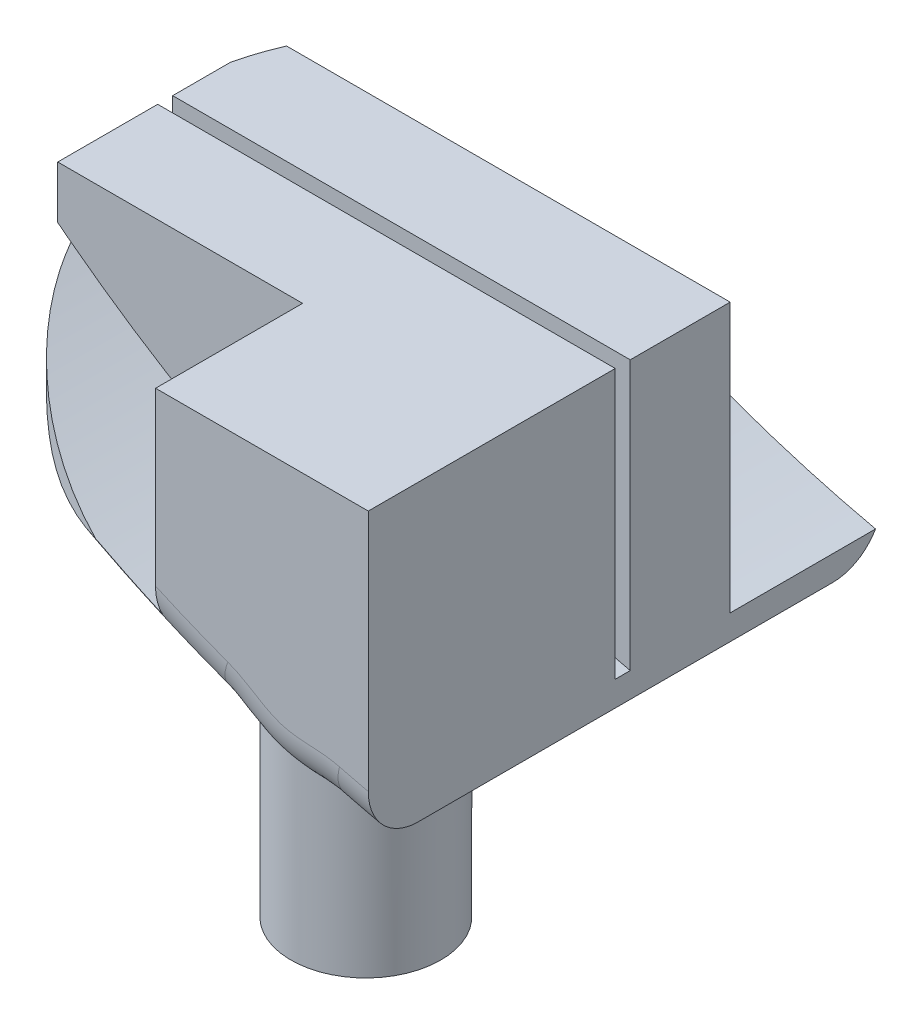
SolidWorks part; units mm, degrees
ref_plane "Front Plane" through (0, 0, 0) normal (0, 0, 1) x (1, 0, 0)
ref_plane "Top Plane" through (0, 0, 0) normal (0, 1, 0) x (1, 0, 0)
ref_plane "Right Plane" through (0, 0, 0) normal (1, 0, 0) x (0, 0, -1)
sketch "Sketch1" plane through (0, 0, 0) normal (0, 1, 0) x (1, 0, 0)
  line L1 (-101.7931, 82.9144) -> (50.6503, 82.9144)
  line L2 (-101.7931, 82.9144) -> (-101.7931, -53.7229)
  line L3 (-101.7931, -53.7229) -> (50.6503, -53.7229)
  line L4 (50.6503, 82.9144) -> (50.6503, -53.7229)
  line L5 (-101.7931, 82.9144) -> (50.6503, -53.7229) construction
  line L6 (-101.7931, -53.7229) -> (50.6503, 82.9144) construction
  point P0 (-25.5714, 14.5958)
extrude "Boss-Extrude1" add sketch "Sketch1" along normal blind 200
sketch "Sketch2" plane through (0, 0, 0) normal (0, 0, 1) x (1, 0, 0)
  line L2 (-83, 153) -> (-80, 153)
  line L4 (-155, -69.5) -> (-155, -64.5)
  line L9 (-155, -64.5) -> (-152, -64.5)
  line L12 (-152, -64.5) -> (-152, -59.5)
  line L13 (-152, -59.5) -> (-155, -59.5)
  line L14 (-155, -59.5) -> (-155, -54.0482)
  line L15 (-288.0952, 47) -> (-296.5952, 47)
  line L17 (-296.5952, 47) -> (-296.5952, 44)
  line L19 (-296.5952, 44) -> (-287.9228, 44)
  line L21 (-83, 160.5) -> (-80, 160.5)
  line L22 (-80, 160.5) -> (-80, 153)
  line L23 (-83, 153) -> (-83, 145.5)
  parabola Q1 (-155, -69.5) -> (-306.0893, 45.5) focus (-179.0197, 57.3821) apex (-244.7409, -27.552)
  spline S1 degree 3 poles (-83, 160.5) (-186.6749, 160.5) (-259.8996, 132.37) (-306.0893, 45.5) knots 0 0 0 0 1 1 1 1
  spline S2 degree 1 poles (-151.4967, -54.9148) (-288.8909, 45.6217) knots 0 0 1 1 construction
  spline S3 degree 1 poles (-83, 145.5) (-288.8909, 45.6217) knots 0 0 1 1 construction
  spline S4 degree 3 poles (-151.4967, -54.9148) (-153.3988, -54.458) (-157.2086, -53.4983) (-164.6601, -51.4419) (-173.7484, -48.594) (-184.2693, -44.7413) (-197.7998, -39.024) (-213.7896, -30.7928) (-231.5494, -19.1756) (-247.9291, -5.7971) (-260.462, 6.8492) (-269.8307, 17.8876) (-276.5289, 26.6314) (-281.8406, 34.3147) (-285.9211, 40.691) (-287.9161, 43.9748) (-288.8909, 45.6217) knots 0.497669 0.497669 0.497669 0.497669 0.497806 0.497943 0.498217 0.498491 0.498765 0.499314 0.499862 0.500411 0.500959 0.501233 0.501508 0.501782 0.501919 0.502056 0.502056 0.502056 0.502056 only from (-155, -54.0482) to (-287.9228, 44)
  spline S5 degree 3 poles (-288.8909, 45.6217) (-288.2118, 46.8068) (-286.8274, 49.1771) (-284.0331, 53.7809) (-280.4563, 59.3452) (-276.0412, 65.7051) (-269.9863, 73.7792) (-262.1032, 83.1283) (-252.1296, 93.2247) (-241.6235, 102.2655) (-226.87, 112.9967) (-206.9505, 124.0773) (-184.8372, 132.3478) (-165.7316, 137.4023) (-150.6813, 140.4388) (-134.8993, 142.7481) (-121.1337, 144.0897) (-109.751, 144.8283) (-101.0301, 145.2187) (-93.6051, 145.4111) (-87.5802, 145.4874) (-84.523, 145.5) (-83, 145.5) knots 0 0 0 0 0.015161 0.030323 0.060645 0.090968 0.12129 0.181936 0.242581 0.303226 0.363871 0.485162 0.606452 0.667098 0.727743 0.788388 0.849033 0.879356 0.909679 0.940001 0.955163 0.970324 0.970324 0.970324 0.970324 only from (-288.0952, 47) to (-83, 145.5)
  dimension "D2" = 7.5
  dimension "D3" = 5
  dimension "D4" = 5
  dimension "D5" = 8.5
  dimension "D1" = 15
sketch "Sketch3" plane through (-101.7931, 0, 0) normal (-1, 0, 0) x (0, 0, 1)
  line L1 (53.7229, 0) -> (-82.9144, 0)
  line L2 (53.7229, 0) -> (53.7229, 200)
  line L3 (53.7229, 200) -> (-82.9144, 200)
  line L4 (-82.9144, 0) -> (-82.9144, 200)
extrude "Boss-Extrude2" add sketch "Sketch3" along normal blind 220
sketch "Sketch4" plane through (0, 0, 0) normal (0, -1, 0) x (-1, 0, 0)
  line L1 (321.7931, 82.9144) -> (-50.6503, 82.9144)
  line L2 (321.7931, 82.9144) -> (321.7931, -53.7229)
  line L3 (321.7931, -53.7229) -> (-50.6503, -53.7229)
  line L4 (-50.6503, 82.9144) -> (-50.6503, -53.7229)
extrude "Boss-Extrude3" add sketch "Sketch4" along normal blind 80
sketch "Sketch5" plane through (0, 0, 0) normal (0, 0, 1) x (1, 0, 0)
  line L0 (-155, -69.5) -> (-155, -80)
  line L1 (50.6503, -80) -> (-321.7931, -80) construction
  line L2 (-155, -69.5) -> (-155, -54.0482)
  line L3 (-244.7409, -27.552) -> (-247.8008, -31.5064)
  line L5 (-155, -69.5) -> (-155, -74.5)
  arc A0 (-155, -69.5) -> (-244.7409, -27.552) centre (-105.1343, 154.1469) cw
  arc A1 (-155, -74.5) -> (-247.8008, -31.5064) centre (-104.6153, 155.9057) cw
extrude "Boss-Extrude4" add sketch "Sketch5" along normal blind 180 contours L5 A1 L3 A0
sketch "Sketch6" plane through (0, 0, 53.7229) normal (0, 0, 1) x (1, 0, 0)
  line L0 (50.6503, -80) -> (-321.7931, -80) construction
  line L1 (-260.7437, -80) -> (-154.9156, -80)
  line L2 (-260.7437, -80) -> (-260.7437, 10.4738)
  line L3 (-260.7437, 10.4738) -> (-154.9156, 10.4738)
  line L4 (-154.9156, -80) -> (-154.9156, 10.4738)
  line L6 (-260.7437, 10.4738) -> (-302.077, 10.4738)
  line L7 (-260.7437, 10.4738) -> (-260.7437, -1.896)
  line L8 (-260.7437, -1.896) -> (-302.077, -1.896)
  line L9 (-302.077, 10.4738) -> (-302.077, -1.896)
  line L10 (-154.9156, 10.4738) -> (-246.5701, 10.4738)
  line L11 (-154.9156, 10.4738) -> (-154.9156, -15.638)
  line L12 (-154.9156, -15.638) -> (-246.5701, -15.638)
  line L13 (-246.5701, 10.4738) -> (-246.5701, -15.638)
extrude "Boss-Extrude6" add sketch "Sketch6" along normal blind 160 contours L3 L13 L12 L4 region at (-200.7429, -2.5821, 53.7229)
sketch "Sketch8" plane through (0, -15.638, 0) normal (0, -1, 0) x (-1, 0, 0)
  line L0 (246.5701, -213.7229) -> (246.5701, -53.7229) construction
  line L1 (246.5701, -82.8166) -> (154.9156, -82.8166)
  line L2 (246.5701, -82.8166) -> (246.5701, -102.8166)
  line L3 (246.5701, -102.8166) -> (154.9156, -102.8166)
  line L4 (154.9156, -82.8166) -> (154.9156, -102.8166)
  line L5 (154.9156, -213.7229) -> (154.9156, -53.7229) construction
  line L6 (154.9156, -102.8166) -> (154.9156, -105.8166)
  line L8 (154.9156, -105.8166) -> (246.5701, -105.8166)
  line L9 (154.9156, -105.8166) -> (154.9156, -125.8166)
  line L10 (154.9156, -125.8166) -> (246.5701, -125.8166)
  line L11 (246.5701, -105.8166) -> (246.5701, -125.8166)
  line M8 (154.9156, -53.7229) -> (154.9156, -213.7229)
  line M10 (246.5701, -213.7229) -> (246.5701, -53.7229)
  dimension "D1" = 20
  dimension "D2" = 20
  dimension "D3" = 3
extrude "Boss-Extrude7" add sketch "Sketch8" along normal up to surface (53.8808 mm away) contours L10 L8 M8 M10 | L3 L1 M10 M8 region at (-200.7429, -15.638, 92.8166) region at (-200.7429, -15.638, 115.8166) up to face at (-201.0175, -50.9798, 116.8614)
sketch "Sketch9" plane through (0, -15.638, 0) normal (0, -1, 0) x (-1, 0, 0)
  line L0 (154.9156, -125.8166) -> (154.9156, -135.8166) construction
  line L1 (154.9156, -213.7229) -> (154.9156, -125.8166) construction
  line L2 (154.9156, -135.8166) -> (174.9156, -135.8166) construction
  circle A0 centre (174.9156, -135.8166) radius 15
extrude "Boss-Extrude8" add sketch "Sketch9" along normal blind 90
sketch "Sketch10" plane through (0, -15.638, 0) normal (0, -1, 0) x (-1, 0, 0)
  line L0 (154.9156, -213.7229) -> (154.9156, -125.8166) construction
  line L1 (246.5701, -125.8166) -> (154.9156, -125.8166)
  line L2 (246.5701, -125.8166) -> (246.5701, -155.2396)
  line L3 (246.5701, -155.2396) -> (154.9156, -155.2396)
  line L4 (154.9156, -125.8166) -> (154.9156, -155.2396)
  line L6 (154.9156, -125.8166) -> (197.5697, -125.8166)
  line L7 (154.9156, -125.8166) -> (154.9156, -155.2396)
  line L8 (154.9156, -155.2396) -> (197.5697, -155.2396)
  line L9 (197.5697, -125.8166) -> (197.5697, -155.2396)
  arc M2 (186.0959, -125.8166) -> (163.7353, -125.8166) centre (174.9156, -135.8166) cw
  line M3 (163.7353, -125.8166) -> (154.9156, -125.8166)
  line M4 (154.9156, -125.8166) -> (154.9156, -213.7229)
extrude "Boss-Extrude9" add sketch "Sketch10" along normal up to surface (39.882 mm away) contours L9 L1 L3 M2 M3 M4 region at (-197.0516, -15.638, 140.5281) up to face at (-191.8541, -54.9413, 143.0605)
sketch "Sketch11" plane through (0, -105.638, 0) normal (0, -1, 0) x (-1, 0, 0)
  line L0 (189.9156, -135.8166) -> (159.9156, -135.8166) construction
  circle A0 centre (174.9156, -135.8166) radius 15 construction
  circle A1 centre (174.9156, -135.8166) radius 15 construction
  circle A2 centre (174.9156, -135.8166) radius 5
extrude "Cut-Extrude1" cut sketch "Sketch11" against normal blind 30 contours A2
sketch "Sketch12" plane through (0, -80, 0) normal (0, -1, 0) x (-1, 0, 0)
  line L1 (-50.6503, 82.9144) -> (321.7931, 82.9144)
  line L2 (-50.6503, 82.9144) -> (-50.6503, -53.7229)
  line L3 (-50.6503, -53.7229) -> (321.7931, -53.7229)
  line L4 (321.7931, 82.9144) -> (321.7931, -53.7229)
extrude "Cut-Extrude2" cut sketch "Sketch12" against normal blind 310
sketch "Sketch13" plane through (-154.9156, 0, 0) normal (1, 0, 0) x (0, 0, -1)
  line L1 (-53.7229, 10.4738) -> (-213.7229, 10.4738)
  line L2 (-53.7229, 10.4738) -> (-53.7229, -15.638)
  line L3 (-53.7229, -15.638) -> (-213.7229, -15.638)
  line L4 (-213.7229, 10.4738) -> (-213.7229, -15.638)
extrude "Cut-Extrude3" cut sketch "Sketch13" against normal blind 310
sketch "Sketch14" plane through (0, 0, 155.2396) normal (0, 0, 1) x (1, 0, 0)
  line L0 (-155, -69.5) -> (-155, -74.5) construction
  line L1 (-155, -69.5992) -> (-154.7887, -69.5992)
  line L2 (-155, -69.5992) -> (-155, -8.2779)
  line L3 (-155, -8.2779) -> (-154.7887, -8.2779)
  line L4 (-154.7887, -69.5992) -> (-154.7887, -8.2779)
  dimension "D1" = 61.3214
extrude "Cut-Extrude4" cut sketch "Sketch14" against normal blind 310 contours L2 L1 L4 L3
sketch "Sketch15" plane through (0, -15.638, 0) normal (0, 1, 0) x (1, 0, 0)
  line L0 (-200.7851, -102.8166) -> (-200.7851, -104.3166)
  line L1 (-155, -53.7229) -> (-247.8008, -53.7229)
  line L2 (-155, -53.7229) -> (-155, -180)
  line L3 (-155, -180) -> (-247.8008, -180)
  line L4 (-247.8008, -53.7229) -> (-247.8008, -180)
  line L5 (-246.5701, -102.8166) -> (-155, -102.8166) construction
  line L6 (-200.7851, -104.3166) -> (-155, -104.3166)
  line L7 (-200.7851, -104.3166) -> (-247.8008, -104.3166)
  line L8 (-247.8008, -104.3166) -> (-247.8008, -53.7229)
  line L9 (-231.1669, -104.3166) -> (-231.1669, -53.7229)
  line L10 (-231.1669, -104.3166) -> (-231.1669, -154.9166)
  line L11 (-231.1669, -154.9166) -> (-155, -155.2396)
  line L12 (-231.1669, -154.9166) -> (-247.8008, -154.9166)
  line L14 (-247.8008, -180) -> (-155, -180)
  line L15 (-247.8008, -180) -> (-247.8008, -155.2396)
  line L16 (-247.8008, -155.2396) -> (-155, -155.2396)
  line L17 (-155, -180) -> (-155, -155.2396)
extrude "Cut-Extrude5" cut sketch "Sketch15" against normal blind 310 contours L16 L4 L3 L2 region at (-201.4004, -15.638, 167.6198)
sketch "Sketch16" plane through (0, -15.638, 0) normal (0, 1, 0) x (1, 0, 0)
  line L0 (-247.8008, -104.4812) -> (-247.8008, -53.7229)
  line L1 (-247.8008, -155.2396) -> (-155, -155.2396)
  line L2 (-247.8008, -155.2396) -> (-247.8008, -53.7229)
  line L3 (-247.8008, -53.7229) -> (-155, -53.7229)
  line L4 (-155, -155.2396) -> (-155, -53.7229)
  line L5 (-247.8008, -53.7229) -> (-201.4004, -53.7229)
  arc A0 (-247.8008, -104.4812) -> (-201.4004, -53.7229) centre (-199.2214, -102.3023) cw
  arc A1 (-247.8008, -104.4812) -> (-201.4004, -155.2396) centre (-199.2214, -106.6602) ccw
  line M3 (-246.5701, -105.8166) -> (-246.5701, -125.8166)
  line M4 (-246.5701, -125.8166) -> (-197.5697, -125.8166)
extrude "Cut-Extrude6" cut sketch "Sketch16" against normal blind 160 contours L2 A0 L3 | A1 L2 L1 M4 M3 region at (-236.9964, -15.638, 64.5273) region at (-236.8255, -15.638, 144.8495)
sketch "Sketch17" plane through (0, 0, 155.2396) normal (0, 0, 1) x (1, 0, 0)
  line L0 (-155, -74.5) -> (-242.5695, -74.5)
  line L1 (-246.5701, -26.1318) -> (-255.4917, -29.1853)
  line L2 (-244.7409, -27.552) -> (-243.9175, -28.1818)
  line L3 (-243.9175, -28.1818) -> (-239.5771, -39.1571)
  line L4 (-239.5771, -39.1571) -> (-257.0025, -32.1063)
  line L5 (-257.0025, -32.1063) -> (-244.7409, -27.552)
extrude "Cut-Extrude7" cut sketch "Sketch17" against normal blind 160 contours L5 L4 L3 L2 region at (-246.9471, -32.8906, 155.2396)
fillet "Fillet1" radius 20 1 edges at (-240.4769, -36.8818, 104.4812)
fillet "Fillet2" radius 10 1 edges at (-178.5983, -68.0405, 155.2396)
fillet "Fillet3" radius 10 1 edges at (-178.5983, -68.0405, 53.7229)
